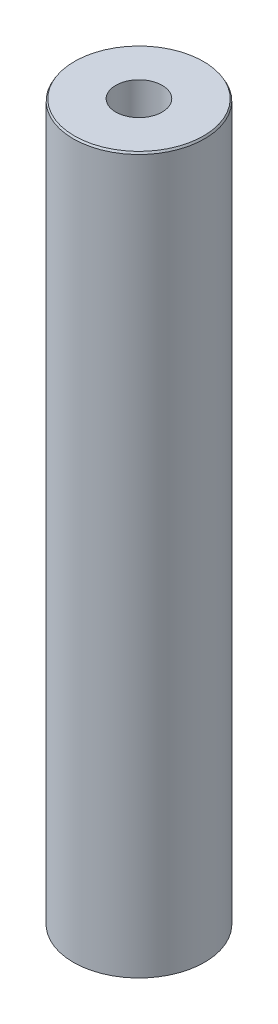
SolidWorks part; units mm, degrees
ref_plane "Front Plane" through (0, 0, 0) normal (0, 0, 1) x (1, 0, 0)
ref_plane "Top Plane" through (0, 0, 0) normal (0, 1, 0) x (1, 0, 0)
ref_plane "Right Plane" through (0, 0, 0) normal (1, 0, 0) x (0, 0, -1)
sketch "Sketch1" plane through (0, 0, 0) normal (0, 1, 0) x (1, 0, 0)
  circle A0 centre (0, 0) radius 55
  dimension "SHAFT_OD" = 110
extrude "Boss-Extrude1" add sketch "Sketch1" along normal blind 600
sketch "Sketch2" plane through (0, 0, 0) normal (0, 1, 0) x (1, 0, 0)
  circle A0 centre (0, 0) radius 19.4403
  dimension "BORE_D" = 38.8807
extrude "Cut-Extrude1" cut sketch "Sketch2" along normal through all
chamfer "Chamfer1" distance 1.6204 angle 30 2 edges at (0, 600, 55) (0, 0, 55) first distance on face at (0, 600, 55) first distance on face at (0, 0, 19.4403)
